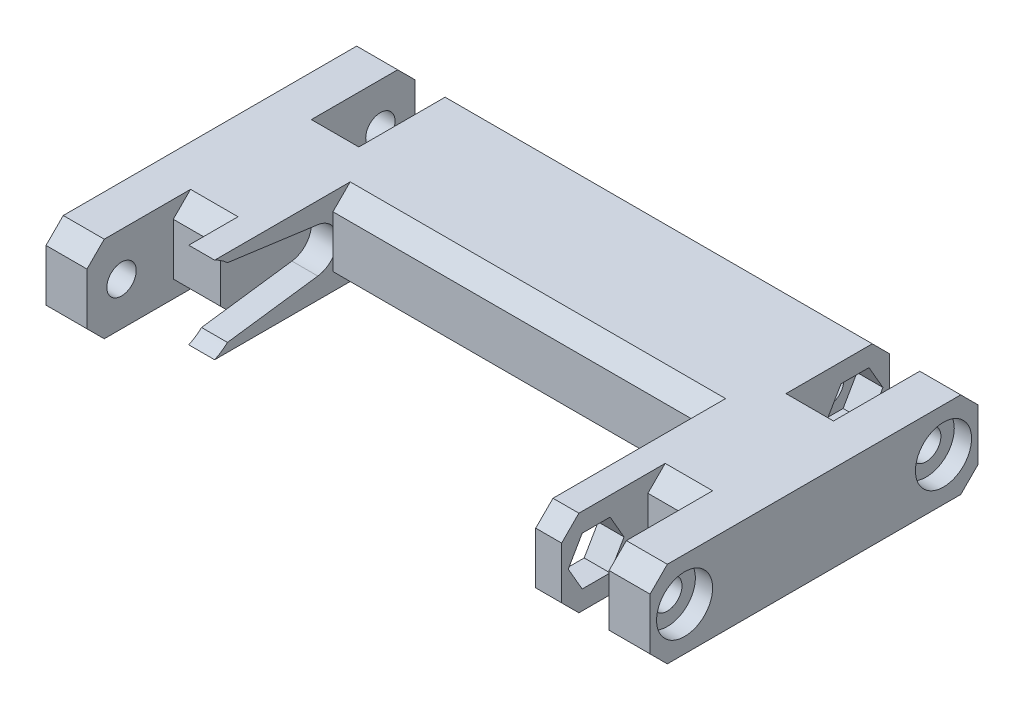
SolidWorks part; units mm, degrees
ref_plane "Front Plane" through (0, 0, 0) normal (0, 0, 1) x (1, 0, 0)
ref_plane "Top Plane" through (0, 0, 0) normal (0, 1, 0) x (1, 0, 0)
ref_plane "Right Plane" through (0, 0, 0) normal (1, 0, 0) x (0, 0, -1)
sketch "Sketch1" plane through (0, 0, 0) normal (0, 1, 0) x (1, 0, 0)
  line L1 (-35, -19) -> (35, -19)
  line L2 (-35, -19) -> (-35, 19)
  line L3 (-35, 19) -> (35, 19)
  line L4 (35, -19) -> (35, 19)
  line L5 (-35, -19) -> (35, 19) construction
  line L6 (-35, 19) -> (35, -19) construction
  point P0 (0, 0)
  dimension "D1" = 70
  dimension "D2" = 38
extrude "Boss-Extrude1" add sketch "Sketch1" along normal blind 10
sketch "Sketch2" plane through (0, 10, 0) normal (0, 1, 0) x (1, 0, 0)
  line L0 (35, 19) -> (-35, 19) construction
  line L1 (-30.25, 19) -> (-24.75, 19)
  line L2 (-30.25, 19) -> (-30.25, 9)
  line L3 (-30.25, 9) -> (-24.75, 9)
  line L4 (-24.75, 19) -> (-24.75, 9)
  line L5 (0, 0) -> (0, 19) construction
  line L6 (24.75, 19) -> (24.75, 9)
  line L7 (30.25, 9) -> (24.75, 9)
  line L8 (30.25, 19) -> (30.25, 9)
  line L9 (30.25, 19) -> (24.75, 19)
  dimension "D1" = 5.5
  dimension "D2" = 10
  dimension "D3" = 49.5
extrude "Cut-Extrude1" cut sketch "Sketch2" against normal through all
hole_wizard "CBORE for M3 Cheese Head Screw1" positions "Sketch7" profile "Sketch8" counterbore size "M3" standard "ISO"
sketch "Sketch7" plane through (35, 0, 0) normal (1, 0, 0) x (0, 0, -1)
  line L0 (-19, 10) -> (19, 10) construction
  line L1 (19, 10) -> (19, 0) construction
  point P0 (15, 5)
  dimension "D1" = 5
  dimension "D2" = 4
sketch "Sketch8" plane through (35, 5, -15) normal (0, 1, 0) x (0, 0, -1)
  line L0 (0, 0) -> (0, 16.0215)
  line L1 (0, 16.0215) -> (1.7, 15)
  line L2 (1.7, 15) -> (1.7, 2)
  line L3 (1.7, 2) -> (3.25, 2)
  line L4 (3.25, 2) -> (3.25, 0)
  line L5 (3.25, 0) -> (0, 0)
  line L10 (0, 16.0215) -> (-1.7, 15) construction
  line L11 (0, -6.35) -> (0, 107.95) construction
  dimension "Hole Dia." = 3.4
  dimension "Hole Depth" = 15
  dimension "C'Bore Dia." = 6.5
  dimension "C'Bore Depth" = 2
  dimension "Drill Angle" = 118
sketch "Sketch9" plane through (24.75, 0, 0) normal (1, 0, 0) x (0, 0, -1)
  line L1 (16.6166, 7.8) -> (13.3834, 7.8)
  line L2 (13.3834, 7.8) -> (11.7668, 5)
  line L3 (11.7668, 5) -> (13.3834, 2.2)
  line L4 (13.3834, 2.2) -> (16.6166, 2.2)
  line L5 (16.6166, 2.2) -> (18.2332, 5)
  line L6 (18.2332, 5) -> (16.6166, 7.8)
  circle A0 centre (15, 5) radius 2.8 construction
  dimension "D1" = 5.6
extrude "Cut-Extrude2" cut sketch "Sketch9" against normal blind 3
mirror "Mirror1" about plane through (0, 0, 0) normal (1, 0, 0) of "Cut-Extrude2", "CBORE for M3 Cheese Head Screw1"
mirror "Mirror2" about plane through (0, 0, 0) normal (0, 0, 1) of "Cut-Extrude1", "CBORE for M3 Cheese Head Screw1", "Cut-Extrude2", "Mirror1"
chamfer "Chamfer1" distance 2 angle 45 12 edges at (32.625, 0, -19) (32.625, 10, -19) (0, 0, -19) (0, 10, -19) (-32.625, 0, -19) (-32.625, 10, -19) (-32.625, 0, 19) (32.625, 0, 19) (0, 0, 19) (32.625, 10, 19) (-32.625, 10, 19) (0, 10, 19)
sketch "Sketch10" plane through (0, 10, 0) normal (0, 1, 0) x (1, 0, 0)
  line L0 (24.75, -19) -> (-24.75, -19) construction
  line L1 (-21.75, -19) -> (21.75, -19)
  line L2 (-21.75, -19) -> (-21.75, 1)
  line L3 (-21.75, 1) -> (21.75, 1)
  line L4 (21.75, -19) -> (21.75, 1)
  line L6 (-24.75, -9) -> (-24.75, -17) construction
  line L7 (24.75, -17) -> (24.75, -9) construction
  dimension "D1" = 3
  dimension "D2" = 20
  dimension "D3" = 3
extrude "Cut-Extrude3" cut sketch "Sketch10" against normal through all
chamfer "Chamfer2" distance 2 angle 45 2 edges at (0, 0, -1) (0, 10, -1)
chamfer "Chamfer3" distance 2 angle 45 8 edges at (27.5, 0, -9) (27.5, 10, -9) (-27.5, 0, 9) (-27.5, 0, -9) (-27.5, 10, 9) (-27.5, 10, -9) (27.5, 0, 9) (27.5, 10, 9)
sketch "Sketch12" plane through (-21.75, 0, 0) normal (1, 0, 0) x (0, 0, -1)
  line L0 (-11.2251, 1) -> (-0.7499, 2.4237)
  line L1 (-0.7499, 7.5763) -> (-11.2251, 9)
  line L2 (-15, 5) -> (-1.1, 5) construction
  line L3 (-15, -0.5) -> (-15, 10.5) construction
  line L4 (-15, 10.5) -> (-19, 10.5)
  line L5 (-19, 10.5) -> (-19, -0.5)
  line L6 (-19, -0.5) -> (-15, -0.5)
  line L7 (-19, 8) -> (-19, 2) construction
  line L8 (-20.5, 5) -> (-15, 5) construction
  line L9 (-1.1, 5) -> (1.5, 5) construction
  circle A0 centre (-15, 5) radius 5.5 construction
  arc A1 (-0.7499, 2.4237) -> (-0.7499, 7.5763) centre (-1.1, 5) ccw
  arc A2 (-11.2251, 9) -> (-15, 10.5) centre (-15, 5) ccw
  arc A3 (-11.2251, 1) -> (-15, -0.5) centre (-15, 5) cw
  dimension "D1" = 11
  dimension "D2" = 8
  dimension "D3" = 2.6
  dimension "D4" = 22
extrude "Cut-Extrude5" cut sketch "Sketch12" against normal up to surface (3 mm away) up to face at (-24.75, 5, 15)
